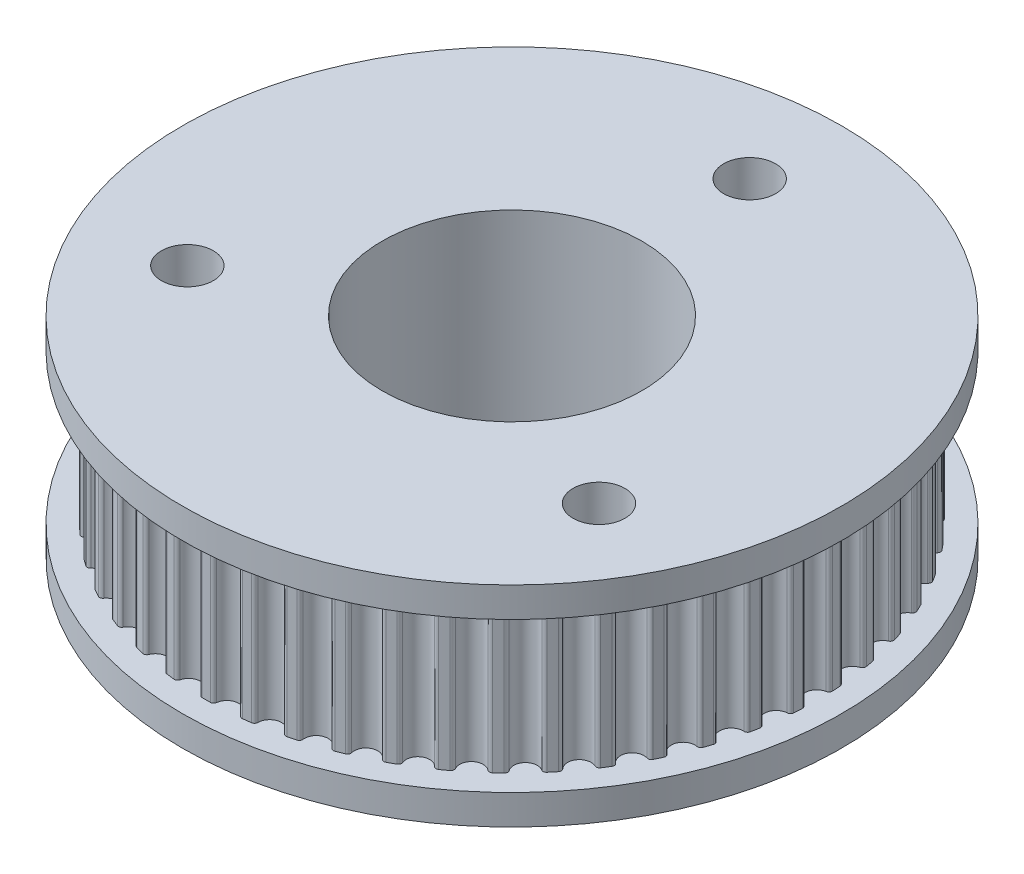
SolidWorks part; units mm, degrees
ref_plane "Front Plane" through (0, 0, 0) normal (0, 0, 1) x (1, 0, 0)
ref_plane "Top Plane" through (0, 0, 0) normal (0, 1, 0) x (1, 0, 0)
ref_plane "Right Plane" through (0, 0, 0) normal (1, 0, 0) x (0, 0, -1)
sketch "mountingHoles" plane through (0, 0, 0) normal (0, 1, 0) x (1, 0, 0)
  line L0 (0, 26.924) -> (0, 16.51) construction
  circle A0 centre (0, 0) radius 39.751
  circle A2 centre (0, 30.226) radius 3.302
  circle A6 centre (26.1765, -15.113) radius 3.302
  circle A10 centre (-26.1765, -15.113) radius 3.302
  circle A11 centre (0, 0) radius 16.51
  circle A13 centre (26.1765, 15.113) radius 3.302 [skipped]
  circle A14 centre (-26.1765, 15.113) radius 3.302 [skipped]
  circle A15 centre (0, -30.226) radius 3.302 [skipped]
  point P26 (0, 0)
  dimension "D1" = 79.502
  dimension "D2" = 33.02
  dimension "D3" = 10.414
  dimension "D4" = 6.604
  dimension "D5" = 6
extrude "Boss-Extrude1" add sketch "mountingHoles" along normal mid plane 19.05 contours A0
sketch "Sketch2" plane through (0, 9.525, 0) normal (0, 1, 0) x (1, 0, 0)
  line L0 (0, 0) -> (0, 39.4817) construction
  line L1 (0, 0) -> (2.4339, 38.6854) construction
  line L2 (0, 38.8874) -> (0, 39.751)
  line L3 (2.4339, 38.6854) -> (2.496, 39.6726) construction
  line L4 (4.8739, 38.5808) -> (4.9821, 39.4376)
  arc A0 (0, 38.8874) -> (0.5234, 38.8839) centre (0, 0) cw
  arc A1 (0.5234, 38.8839) -> (0.9463, 38.5043) centre (0.5176, 38.4521) cw
  arc A2 (0.9463, 38.5043) -> (3.8871, 38.3193) centre (2.4339, 38.6854) ccw
  circle A3 centre (0, 0) radius 39.751 construction
  arc A4 (4.3541, 38.6429) -> (3.8871, 38.3193) centre (4.3058, 38.2138) ccw
  arc A5 (4.8739, 38.5808) -> (4.3541, 38.6429) centre (0, 0) ccw
  arc A6 (0, 39.751) -> (4.9821, 39.4376) centre (0, 0) cw
  dimension "D3" = 0.8636
  dimension "D4" = 3.6
  dimension "D2" = 1.4986
  dimension "D1" = 0.4318
extrude "Cut-Extrude1" cut sketch "Sketch2" against normal blind 19.05 contours A6 L4 A5 A4 A2 A1 A0 L2
pattern_circular "CirPattern1" count 50 over 360 about axis through (0, 9.525, 0) along (0, -1, 0) of "Cut-Extrude1" reverse direction yes
sketch "flange" plane through (0, 9.525, 0) normal (0, 1, 0) x (1, 0, 0)
  circle A0 centre (0, 0) radius 41.91
extrude "Boss-Extrude2" add sketch "flange" along normal blind 3.81 contours A0
sketch "Sketch6" plane through (0, -9.525, 0) normal (0, -1, 0) x (1, 0, 0)
  circle A0 centre (0, 0) radius 41.91
extrude "Boss-Extrude3" add sketch "Sketch6" along normal blind 3.81
extrude "Cut-Extrude5" cut sketch "Sketch1<5>" against normal blind 31.242 and the other way blind 32.512 contours A2 | A11 | A6 | A10
sketch "Sketch1<5>" plane through (0, 0, 0) normal (0, 1, 0) x (1, 0, 0) same geometry as "mountingHoles"
equation "\"n\"= 50"
equation "\"p\"= 5mm"
equation "\"pd\"= \"n\" * \"p\" / 3.1415926"
